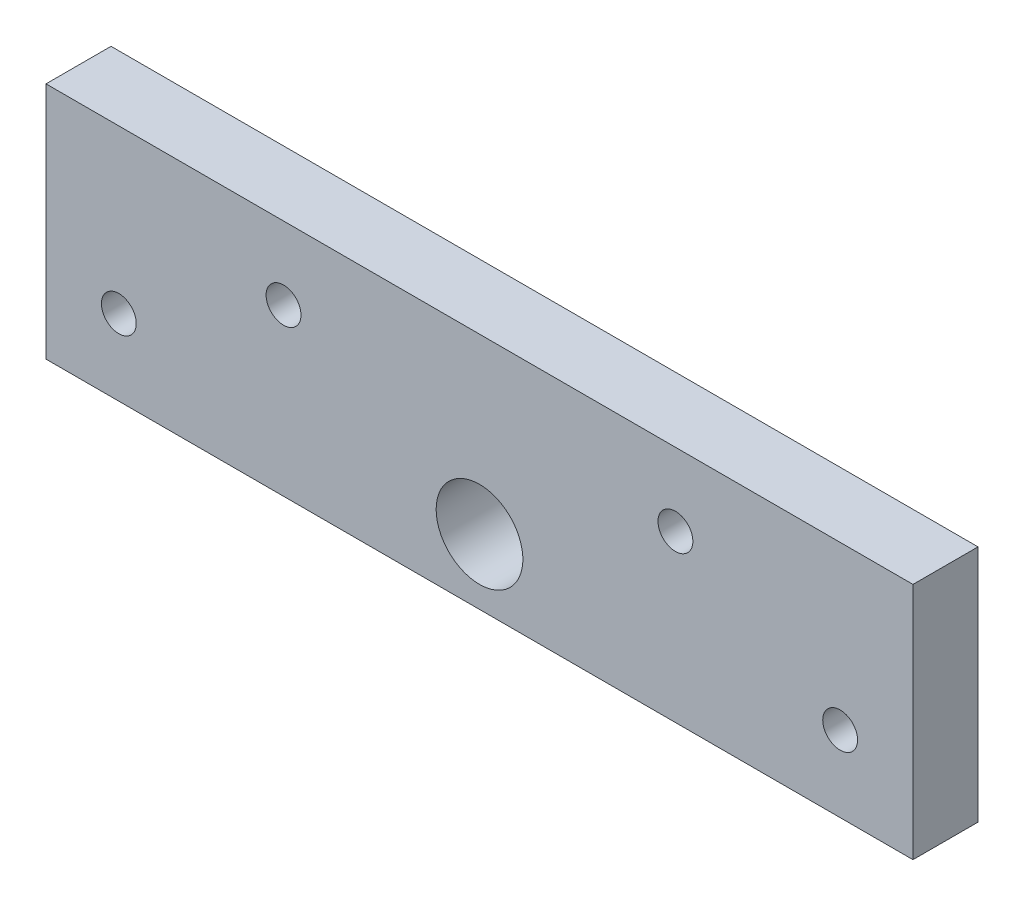
SolidWorks part; units mm, degrees
material "6061-T6 (SS)"
ref_plane "Front Plane" through (0, 0, 0) normal (0, 0, 1) x (1, 0, 0)
ref_plane "Top Plane" through (0, 0, 0) normal (0, 1, 0) x (1, 0, 0)
ref_plane "Right Plane" through (0, 0, 0) normal (1, 0, 0) x (0, 0, -1)
sketch "Sketch8" plane through (0, 0, 0) normal (0, 0, 1) x (1, 0, 0)
  line B0 (-63.5, -15.875) -> (63.5, -15.875)
  line B1 (63.5, -15.875) -> (63.5, 0)
  line B2 (36.5092, 0) -> (47.625, 15.875)
  line B3 (47.625, 15.875) -> (16.0563, 15.875)
  line B4 (-39.8731, 15.875) -> (-28.7573, 0)
  line B5 (-28.7573, 0) -> (-63.5, 0)
  line B6 (-36.5092, 0) -> (-47.625, 15.875)
  line B7 (-47.625, 15.875) -> (-39.8731, 15.875)
  line B8 (-16.0563, 15.875) -> (-16.0563, -3.175)
  line B9 (-16.0563, -3.175) -> (16.0563, -3.175)
  line B10 (16.0563, -3.175) -> (16.0563, 15.875)
  line B11 (-16.0563, 15.875) -> (-39.8731, 15.875)
  line B12 (-63.5, 0) -> (-63.5, 31.75)
  line B13 (-63.5, 31.75) -> (63.5, 31.75)
  line B14 (-16.0563, 15.875) -> (16.0563, 15.875)
  line B15 (0, 31.75) -> (0, -15.875) construction
  line B16 (-36.5092, 0) -> (36.5092, 0) construction
  line B17 (-28.702, 21.082) -> (28.702, 21.082) construction
  line B18 (-25.4, -8.001) -> (25.4, -8.001) construction
  line B19 (-25.4, -8.001) -> (-25.4, 7.9375) construction
  line B20 (-52.832, 7.9375) -> (52.832, 7.9375) construction
  circle B21 centre (0, 6.35) radius 18.669 construction
  line B22 (39.8731, 15.875) -> (28.7573, 0)
sketch_block_instance "dovetail pair-1"
sketch_block "Block1" parameters "D8"=37.338, "D1"=55, "D2"=127, "D3"=6.35, "D4"=15.875, "D5"=31.75, "D6"=95.25, "D7"=19.05, "D9"=55, "D10"=31.75, "D11"=50.8, "D12"=23.876, "D13"=7.874, "D14"=10.668, "D15"=34.798, "D16"=21.082, "D17"=7.9375
sketch "Sketch1" plane through (0, 0, 0) normal (0, 0, 1) x (1, 0, 0)
  line L0 (63.5, -15.875) -> (63.5, 0) construction
  line L1 (-63.5, 31.75) -> (63.5, 31.75)
  line L2 (-63.5, 31.75) -> (-63.5, -3.175)
  line L3 (-63.5, -3.175) -> (63.5, -3.175)
  line L4 (63.5, 31.75) -> (63.5, -3.175)
  line L5 (-16.0563, -3.175) -> (16.0563, -3.175) construction
  circle A0 centre (0, 6.35) radius 6.35
  dimension "D1" = 12.7
extrude "Boss-Extrude1" add sketch "Sketch1" along normal blind 9.525
hole_wizard "CBORE for #10 Socket Head Cap Screw1" positions "Sketch6" profile "Sketch7" counterbore size "#10" standard "ANSI Inch" end condition up to next
sketch "Sketch6" plane through (248.3324, -44.45, 0) normal (0, 0, -1) x (-1, 0, 0)
  point P26 (219.6304, 65.532)
  point P28 (195.5004, 52.3875)
  point P30 (277.0344, 65.532)
  point P32 (301.1644, 52.3875)
sketch "Sketch7" plane through (28.702, 21.082, 0) normal (1, 0, 0) x (0, 1, 0)
  line L0 (0, 0) -> (0, 9.525)
  line L1 (0, 9.525) -> (2.5527, 9.525)
  line L3 (2.5527, 9.525) -> (2.5527, 4.826)
  line L4 (4.7625, 4.826) -> (2.5527, 4.826)
  line L5 (4.7625, 4.826) -> (4.7625, 0.635)
  line L6 (4.7625, 0.635) -> (5.3975, 0)
  line L7 (5.3975, 0) -> (0, 0)
  line L8 (-4.7625, 0.635) -> (-5.3975, 0) construction
  line L11 (0, -6.35) -> (0, 107.95) construction
  dimension "Thru Hole Dia." = 5.1054
  dimension "Thru Hole Depth" = 9.525
  dimension "C'Bore Dia." = 9.525
  dimension "C'Bore Depth" = 4.826
  dimension "Near C'Sink Dia." = 10.795
  dimension "Near C'Sink Angle" = 90
equation "\"dovetail-angle\" = 60"
equation "\"dovetail-stock-width\" = 5"
equation "\"dovetail-stock-height\" = 1.25"
equation "\"dovetail-depth\" = 0.5 * \"dovetail-stock-height\""
equation "\"dovetail-throat-width\" = \"dovetail-stock-width\" - (2 * \"dovetail-depth\")"
equation "\"delta-x\" = 6"
equation "\"delta-y\" = 3"
equation "\"gib-thickness\" = 0.25"
equation "\"x-slide-length\" = \"dovetail-stock-width\" + \"delta-x\""
equation "\"y-slide-length\" = \"dovetail-stock-width\" + \"delta-y\""
equation "\"dog-point-diam\" = .149"
equation "\"dog-point-length\" = .067"
equation "\"dovetail-double-height\" = 2 * \"dovetail-depth\" + 0.5"
equation "\"acme-major-diam\" = .5"
equation "\"acme-pitch-diam\" = 0.45"
equation "\"acme-minor-diam\" = 0.4"
equation "\"x-screw-length\" = \"x-slide-length\" + \"screw-add-length\""
equation "\"y-screw-length\" = \"y-slide-length\" + \"screw-add-length\""
equation "\"acme-nut-od\" = 1.47"
equation "\"acme-nut-length\" = 1"
equation "\"acme-nut-trim-height\" = .75"
equation "\"D1@Sketch1\"=\"screw-bearing-od\""
equation "\"screw-bearing-od\" = 0.5"
equation "\"screw-bearing-length\" = .375"
equation "\"end-plate-thickness\" = \"screw-bearing-length\""
equation "\"D1@Boss-Extrude1\"=\"end-plate-thickness\""
equation "\"screw-bearing-id\" = .375"
equation "\"screw-add-length\" = 2 * \"end-plate-thickness\" + 1 + 0.5"
equation "\"acme-nut-mount-hole-space-horz\" = 0.95"
equation "\"acme-nut-mount-hole-space-vert\" = 0.5 * \"acme-nut-length\""
